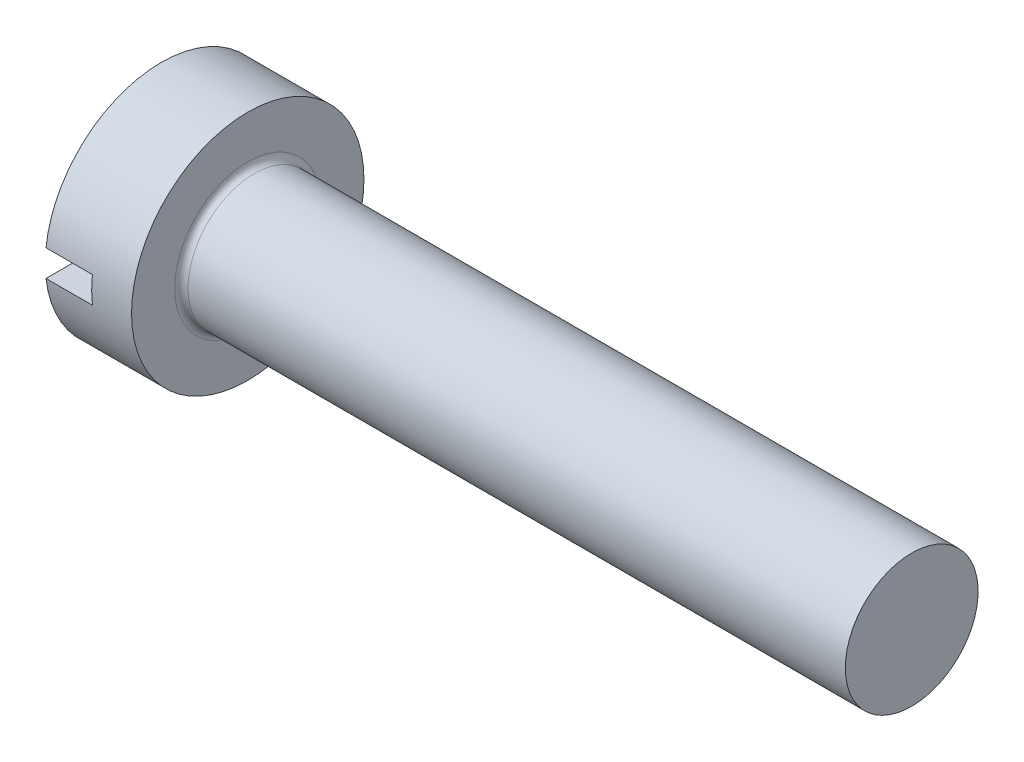
SolidWorks part; units mm, degrees
ref_plane "Front Plane" through (0, 0, 0) normal (0, 0, 1) x (1, 0, 0)
ref_plane "Top Plane" through (0, 0, 0) normal (0, 1, 0) x (1, 0, 0)
ref_plane "Right Plane" through (0, 0, 0) normal (1, 0, 0) x (0, 0, -1)
sketch "BodySke" plane through (0, 0, 0) normal (0, 0, 1) x (1, 0, 0)
  line L0 (0, 0) -> (120.5141, 0) construction
  line L1 (0, 0) -> (0, 50.5629) construction
  line L2 (5.2, 7) -> (5.2, 4)
  line L3 (5.2, 4) -> (45.2, 4)
  line L4 (45.2, 4) -> (45.2, 0)
  line L5 (0, 0) -> (45.2, 0)
  line L6 (5.2, 7) -> (0, 7)
  line L7 (6.45, 10.4217) -> (6.45, -3.1786) construction
  line L8 (15.2, 9.5609) -> (15.2, -6.7938) construction
  line L9 (0, 7) -> (0, 0)
  point P14 (45.2, 3.3095)
  dimension "Thread_minor" = 6.619
  dimension "Advance" = 1.25
revolve "BaseBody" add sketch "BodySke" angle 360 about L0
cosmetic thread "ThreadCosmetic" [suppressed] parameters "Thread_minor"=6.619
fillet "Fillet1" radius 0.4 1 edges at (5.2, 0, 4)
sketch "SlotSke" plane through (0, 0, 0) normal (1, 0, 0) x (0, 0, -1)
  line L1 (7, 0.8) -> (-7, 0.8)
  line L2 (7, 0.8) -> (7, -0.8)
  line L3 (7, -0.8) -> (-7, -0.8)
  line L4 (-7, 0.8) -> (-7, -0.8)
  dimension "D1" = 14
  dimension "D2" = 7
  dimension "D4" = 0.8
extrude "Slot" cut sketch "SlotSke" along normal blind 2.8
sketch "ThdSchSke" plane through (0, 0, 0) normal (0, 0, 1) x (1, 0, 0)
  line L0 (0, 0) -> (54.7976, 0) construction
  line L1 (44.8013, 4.7973) -> (44.8013, 4)
  line L2 (44.8013, 4.7973) -> (45.5987, 4.7973)
  line L3 (45.5987, 4.7973) -> (45.5987, 4)
  line L4 (45.5987, 4) -> (45.2, 3.3095)
  line L5 (45.2, 3.3095) -> (44.8013, 4)
  line L6 (5.2, 4) -> (45.2, 4) construction
revolve "ThreadSchematic" [suppressed] cut sketch "ThdSchSke" angle 360 about L0
pattern_linear "ThdSchPat" [suppressed] count 24 along (-1, 0, 0) of bodies 103
equation "\"Thread_minor@ThreadCosmetic\" = \"Thread_minor@BodySke\""
equation "\"D1@SlotSke\" = \"Head_dia@BodySke\""
equation "\"D2@SlotSke\" = \"D1@SlotSke\" / 2"
equation "\"D4@SlotSke\" = \"Slot_width@SlotSke\" / 2"
equation "\"Advance@ThdSchPat\" = \"Advance@BodySke\""
equation "\"D1@ThdSchPat\" =  int( \"Thread_length@BodySke\" / \"Advance@BodySke\" ) "
